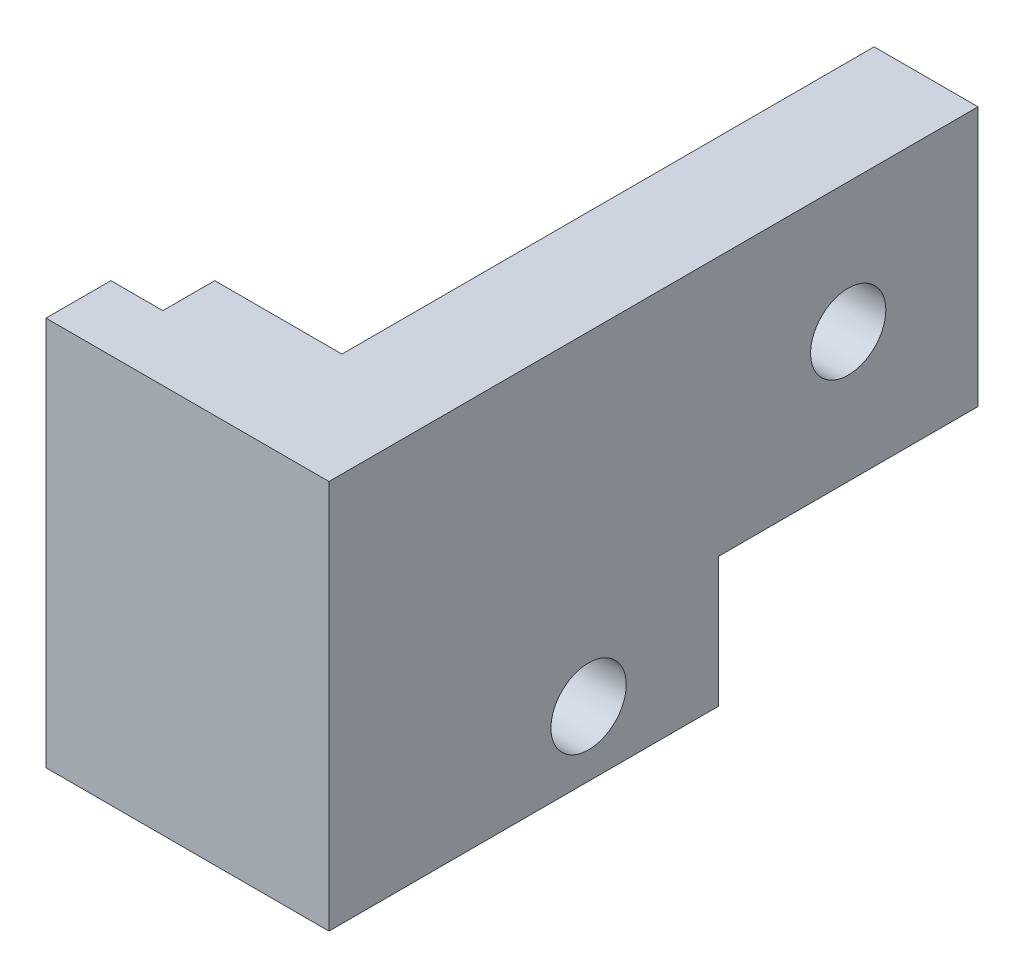
SolidWorks part; units mm, degrees
ref_plane "前视基准面" through (0, 0, 0) normal (0, 0, 1) x (1, 0, 0)
ref_plane "上视基准面" through (0, 0, 0) normal (0, 1, 0) x (1, 0, 0)
ref_plane "右视基准面" through (0, 0, 0) normal (1, 0, 0) x (0, 0, -1)
other "Configuration Table"
sketch "草图1" plane through (0, 0, 0) normal (0, 0, 1) x (1, 0, 0)
  line L1 (0, 0) -> (-40, 0)
  line L2 (0, 0) -> (0, 30)
  line L3 (0, 30) -> (-40, 30)
  line L4 (-40, 0) -> (-40, 30)
  dimension "D1" = 40
  dimension "D2" = 30
extrude "凸台-拉伸1" add sketch "草图1" along normal blind 5
sketch "草图2" plane through (-40, 0, 0) normal (-1, 0, 0) x (0, 0, 1)
  line L4 (0, 30) -> (0, 0)
  line L5 (0, 0) -> (5, 0)
  line L6 (5, 0) -> (5, 30)
  line L7 (5, 30) -> (0, 30)
  line L8 (0, 30) -> (0, 0)
  line L9 (0, 0) -> (5, 0)
  line L10 (5, 0) -> (5, 30)
  line L11 (5, 30) -> (0, 30)
  dimension "D1" = 0
extrude "凸台-拉伸2" add sketch "草图2" along normal blind 20
sketch "草图3" plane through (0, 0, 0) normal (0, 0, -1) x (-1, 0, 0)
  line L0 (60, 0) -> (0, 0) construction
  line L1 (60, 30) -> (40, 30) construction
  line L2 (60, 30) -> (60, 0) construction
  line L3 (60, 0) -> (40, 0) construction
  line L4 (40, 30) -> (40, 0) construction
  line L5 (30, 30) -> (30, 0) construction
  line L6 (0, 30) -> (60, 30) construction
  line L7 (0, 0) -> (20, 0)
  line L8 (20, 30) -> (20, 0)
  line L9 (0, 30) -> (20, 30)
  line L10 (0, 30) -> (0, 0)
  dimension "D1" = 20
extrude "凸台-拉伸3" add sketch "草图3" along normal blind 5
sketch "草图4" plane through (0, 0, 5) normal (0, 0, 1) x (1, 0, 0)
  line L0 (0, 30) -> (-60, 30) construction
  line L1 (-60, 30) -> (-45, 30) construction
  line L2 (-60, 30) -> (-60, 0) construction
  line L3 (-60, 0) -> (-45, 0) construction
  line L4 (-45, 30) -> (-45, 0) construction
  line L5 (-60, 0) -> (0, 0) construction
  line L6 (-60, 0) -> (-60, 30) construction
  line L7 (-30, 30) -> (-30, -4.6416) construction
  line L8 (0, 0) -> (-15, 0)
  line L9 (-15, 30) -> (-15, 0)
  line L10 (0, 30) -> (-15, 30)
  line L11 (0, 30) -> (0, 0)
  dimension "D1" = 0
  dimension "D2" = 15
extrude "切除-拉伸1" cut sketch "草图4" against normal blind 5
sketch "草图6" plane through (0, 0, 0) normal (0, 0, 1) x (1, 0, 0)
  line L0 (-7.5, 30) -> (-7.5, 25) construction
  line L1 (0, 30) -> (-15, 30) construction
  line L2 (-7.5, 25) -> (-7.5, 5) construction
  circle A0 centre (-7.5, 25) radius 1.5
  circle A1 centre (-7.5, 5) radius 1.5
  dimension "D3" = 3
  dimension "D4" = 3
  dimension "D1" = 5
  dimension "D2" = 20
extrude "切除-拉伸3" cut sketch "草图6" against normal blind 5
sketch "草图7" plane through (0, 0, 0) normal (0, 0, 1) x (1, 0, 0)
  line L4 (0, 0) -> (0, 30)
  line L5 (0, 30) -> (-15, 30)
  line L6 (-15, 30) -> (-15, 0)
  line L7 (-15, 0) -> (0, 0)
  line L8 (0, 0) -> (0, 30)
  line L9 (0, 30) -> (-15, 30)
  line L10 (-15, 30) -> (-15, 0)
  line L11 (-15, 0) -> (0, 0)
  dimension "D1" = 0
extrude "切除-拉伸4" cut sketch "草图7" against normal up to surface (5 mm away) up to face at (-6, 25, -5)
sketch "草图8" plane through (0, 0, -5) normal (0, 0, -1) x (-1, 0, 0)
  line L4 (15, 30) -> (15, 0)
  line L5 (15, 0) -> (20, 0)
  line L6 (20, 0) -> (20, 30)
  line L7 (20, 30) -> (15, 30)
  line L8 (15, 30) -> (15, 0)
  line L9 (15, 0) -> (20, 0)
  line L10 (20, 0) -> (20, 30)
  line L11 (20, 30) -> (15, 30)
  dimension "D1" = 0
extrude "凸台-拉伸4" add sketch "草图8" along normal blind 20
sketch "草图9" plane through (-15, 0, 0) normal (1, 0, 0) x (0, 0, -1)
  line L4 (-5, 30) -> (-5, 0)
  line L5 (-5, 0) -> (25, 0)
  line L6 (25, 0) -> (25, 30)
  line L7 (25, 30) -> (-5, 30)
  line L8 (-5, 30) -> (-5, 0)
  line L9 (-5, 0) -> (25, 0)
  line L10 (25, 0) -> (25, 30)
  line L11 (25, 30) -> (-5, 30)
  dimension "D1" = 0
extrude "凸台-拉伸5" add sketch "草图9" along normal blind 3
sketch "草图10" plane through (-12, 0, 0) normal (1, 0, 0) x (0, 0, -1)
  line L0 (25, 30) -> (15, 30) construction
  line L1 (25, 30) -> (-5, 30) construction
  line L2 (15, 30) -> (15, 5) construction
  circle A0 centre (15, 5) radius 1.5
  dimension "D3" = 3
  dimension "D1" = 10
  dimension "D2" = 25
extrude "切除-拉伸5" cut sketch "草图10" against normal blind 13
sketch "草图11" plane through (-12, 0, 0) normal (1, 0, 0) x (0, 0, -1)
  circle A0 centre (15, 5) radius 2.9
  dimension "D1" = 5.8
extrude "切除-拉伸6" cut sketch "草图11" against normal offset from surface (6 mm away) 2 up to face at (-20, 5, -16.5)
sketch "草图12" plane through (0, 0, -25) normal (0, 0, -1) x (-1, 0, 0)
  line L1 (20, 30) -> (12, 30)
  line L2 (20, 30) -> (20, 10)
  line L3 (20, 10) -> (12, 10)
  line L4 (12, 30) -> (12, 10)
  dimension "D1" = 20
extrude "凸台-拉伸6" add sketch "草图12" along normal blind 20
sketch "草图13" plane through (-20, 0, 0) normal (-1, 0, 0) x (0, 0, 1)
  line L0 (-45, 10) -> (-45, 30) construction
  line L1 (-45, 17) -> (-25, 17)
  line L2 (-45, 17) -> (-45, 10)
  line L3 (-45, 10) -> (-25, 10)
  line L6 (-25, 0) -> (-18, 0)
  line L7 (-25, 0) -> (-25, 10)
  line L8 (-25, 17) -> (-18, 17)
  line L9 (-18, 0) -> (-18, 17)
  dimension "D1" = 7
  dimension "D2" = 7
extrude "切除-拉伸7" cut sketch "草图13" against normal blind 4.2
sketch "草图14" plane through (-12, 0, 0) normal (1, 0, 0) x (0, 0, -1)
  line L0 (45, 30) -> (45, 20) construction
  line L1 (45, 30) -> (45, 10) construction
  line L2 (45, 20) -> (35, 20) construction
  circle A0 centre (35, 20) radius 1.5
  dimension "D2" = 3
  dimension "D1" = 10
extrude "切除-拉伸8" cut sketch "草图14" against normal blind 14.2
sketch "草图15" plane through (-12, 0, 0) normal (1, 0, 0) x (0, 0, -1)
  circle A0 centre (35, 20) radius 2.9
  dimension "D1" = 5.8
extrude "切除-拉伸9" cut sketch "草图15" against normal offset from surface (6 mm away) 2 up to face at (-20, 20, -36.5)
sketch "草图16" plane through (-20, 0, 0) normal (-1, 0, 0) x (0, 0, 1)
  line L0 (-18, 0) -> (0, 0) construction
  line L1 (0, 30) -> (-4, 30)
  line L2 (0, 30) -> (0, 0)
  line L3 (0, 0) -> (-4, 0)
  line L4 (-4, 30) -> (-4, 0)
  dimension "D1" = 4
extrude "凸台-拉伸7" add sketch "草图16" along normal blind 9.8
sketch "草图17" plane through (-60, 0, 0) normal (-1, 0, 0) x (0, 0, 1)
  line L4 (5, 30) -> (0, 30)
  line L5 (0, 30) -> (0, 0)
  line L6 (0, 0) -> (5, 0)
  line L7 (5, 0) -> (5, 30)
  line L8 (5, 30) -> (0, 30)
  line L9 (0, 30) -> (0, 0)
  line L10 (0, 0) -> (5, 0)
  line L11 (5, 0) -> (5, 30)
  dimension "D1" = 0
extrude "切除-拉伸10" cut sketch "草图17" against normal offset from surface (26.2 mm away) 4 up to face at (-29.8, 15, -2)
